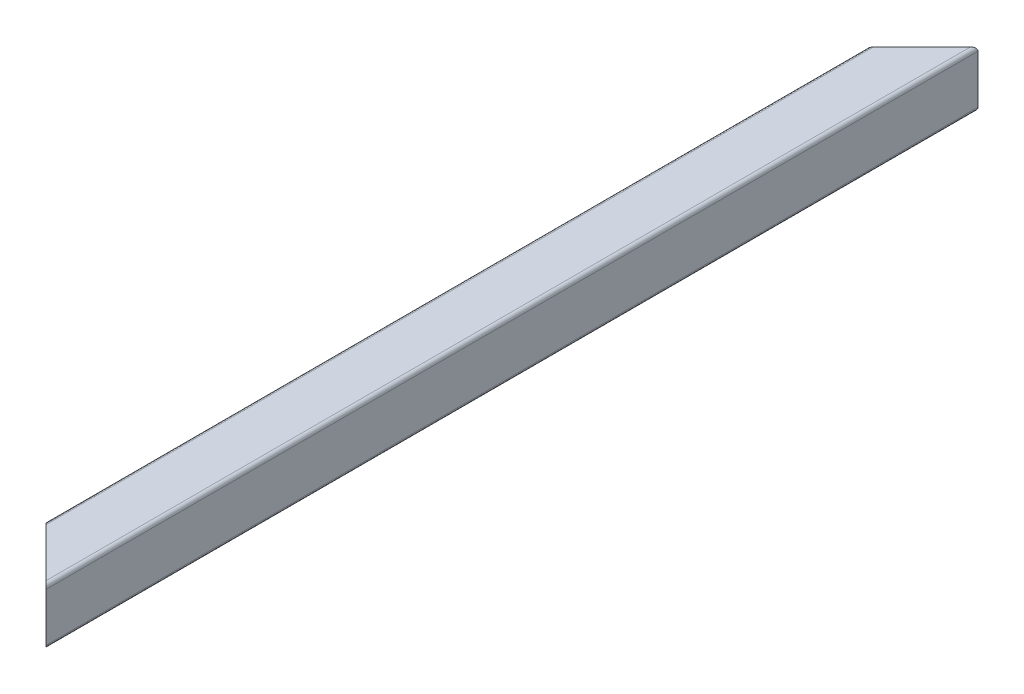
SolidWorks part; units mm, degrees
material "1.4003 (X2CrNi12)"
ref_plane "Ön Düzlem" through (0, 0, 0) normal (0, 0, 1) x (1, 0, 0)
ref_plane "Üst Düzlem" through (0, 0, 0) normal (0, 1, 0) x (1, 0, 0)
ref_plane "Sağ Düzlem" through (0, 0, 0) normal (1, 0, 0) x (0, 0, -1)
sketch "Çizim1" plane through (0, 0, 0) normal (0, 0, 1) x (1, 0, 0)
  line L0 (-13, -13) -> (13, -13)
  line L1 (-13, 15) -> (13, 15)
  line L2 (-15, 13) -> (-15, -13)
  line L3 (-13, -15) -> (13, -15)
  line L4 (15, 13) -> (15, -13)
  line L5 (-15, 15) -> (15, -15) construction
  line L6 (-15, -15) -> (15, 15) construction
  line L7 (13, 13) -> (13, -13)
  line L8 (-13, 13) -> (13, 13)
  line L9 (-13, 13) -> (-13, -13)
  line L10 (15, 15) -> (15, -15) construction
  line L11 (-15, -15) -> (15, -15) construction
  line L12 (-15, 15) -> (-15, -15) construction
  line L13 (-15, 15) -> (15, 15) construction
  arc A0 (15, -13) -> (13, -15) centre (13, -13) cw
  arc A1 (-15, -13) -> (-13, -15) centre (-13, -13) ccw
  arc A2 (13, 15) -> (15, 13) centre (13, 13) cw
  arc A3 (-13, 15) -> (-15, 13) centre (-13, 13) ccw
  point P0 (0, 0)
  dimension "D4" = 2
  dimension "D1" = 30
  dimension "D2" = 30
  dimension "D3" = 2
extrude "Yükseklik-Ekstrüzyon1" add sketch "Çizim1" along normal blind 250 and the other way blind 250
sketch "Çizim2" plane through (0, 0, 0) normal (0, 1, 0) x (1, 0, 0)
  line L0 (15, 250) -> (-15, 220)
  line L1 (-15, 250) -> (-15, -250) construction
  line L2 (-15, 220) -> (-15, 250)
  line L3 (-15, 250) -> (15, 250)
  line L4 (15, -250) -> (-15, -220)
  line L5 (-15, -220) -> (-15, -250)
  line L6 (-15, -250) -> (15, -250)
  dimension "D1" = 45
  dimension "D2" = 45
extrude "Kes-Ekstrüzyon1" cut sketch "Çizim2" against normal blind 250 and the other way blind 250
